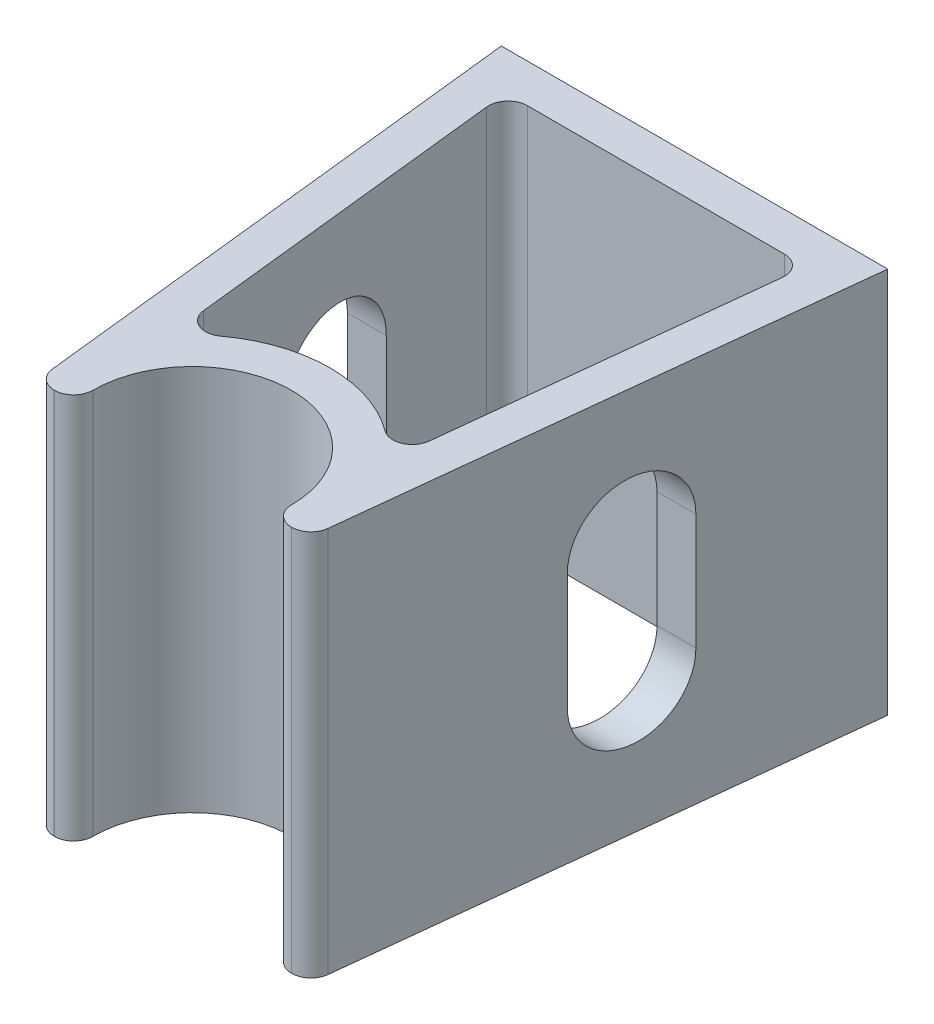
SolidWorks part; units mm, degrees
material "ABS"
ref_plane "Front Plane" through (0, 0, 0) normal (0, 0, 1) x (1, 0, 0)
ref_plane "Top Plane" through (0, 0, 0) normal (0, 1, 0) x (1, 0, 0)
ref_plane "Right Plane" through (0, 0, 0) normal (1, 0, 0) x (0, 0, -1)
sketch "Sketch1" plane through (0, 0, 0) normal (0, 1, 0) x (1, 0, 0)
  line L0 (-12.6, -2.5) -> (-17.6, -2.5)
  line L1 (-17.6, -2.5) -> (-25, 65)
  line L2 (-25, 65) -> (25, 65)
  line L3 (25, 65) -> (17.6, -2.5)
  line L4 (17.6, -2.5) -> (12.6, -2.5)
  arc A0 (12.6, -2.5) -> (-12.6, -2.5) centre (0, 0) ccw
  point P4 (0, 12.8456)
  dimension "D1" = 25.2
  dimension "D2" = 5
  dimension "D3" = 65
  dimension "D4" = 50
  dimension "D5" = 2.5
extrude "Boss-Extrude1" add sketch "Sketch1" along normal blind 50
sketch "Sketch2" plane through (0, 50, 0) normal (0, 1, 0) x (1, 0, 0)
  line L10 (14.0503, 11.0025) -> (19.4219, 60)
  line L11 (19.4219, 60) -> (-19.4219, 60)
  line L12 (-19.4219, 60) -> (-14.0503, 11.0025)
  line L13 (14.0503, 11.0025) -> (19.4219, 60)
  line L14 (19.4219, 60) -> (-19.4219, 60)
  line L15 (-19.4219, 60) -> (-14.0503, 11.0025)
  arc A2 (14.0503, 11.0025) -> (-14.0503, 11.0025) centre (0, 0) ccw
  arc A3 (14.0503, 11.0025) -> (-14.0503, 11.0025) centre (0, 0) ccw
  dimension "D1" = 5
extrude "Cut-Extrude1" cut sketch "Sketch2" against normal through all both and the other way through all
fillet "Fillet2" radius 2.5 8 edges at (-19.4219, 25, -60) (19.4219, 25, -60) (14.0503, 25, -11.0025) (-14.0503, 25, -11.0025) (17.6, 25, 2.5) (12.6, 25, 2.5) (-17.6, 25, 2.5) (-12.6, 25, 2.5)
sketch "Sketch3" plane through (0, 0, 0) normal (1, 0, 0) x (0, 0, -1)
  line L0 (35.1276, 0) -> (35.1276, 50) construction
  line L1 (-0.2724, 0) -> (65, 0) construction
  line L2 (-0.2724, 50) -> (65, 50) construction
  line L3 (35.1276, 32.5) -> (35.1276, 17.5) construction
  line L4 (42.6276, 32.5) -> (42.6276, 17.5)
  line L5 (27.6276, 32.5) -> (27.6276, 17.5)
  arc A1 (42.6276, 32.5) -> (27.6276, 32.5) centre (35.1276, 32.5) ccw
  arc A2 (27.6276, 17.5) -> (42.6276, 17.5) centre (35.1276, 17.5) ccw
  point P10 (35.1276, 25)
  dimension "D1" = 35.4
  dimension "D2" = 15
  dimension "D3" = 15
extrude "Cut-Extrude2" cut sketch "Sketch3" against normal through all both and the other way through all
sketch "Sketch4" plane through (0, 0, -65) normal (0, 0, -1) x (-1, 0, 0)
  text T0 "pratik"
extrude "Boss-Extrude2" add sketch "Sketch4" along normal blind 1
